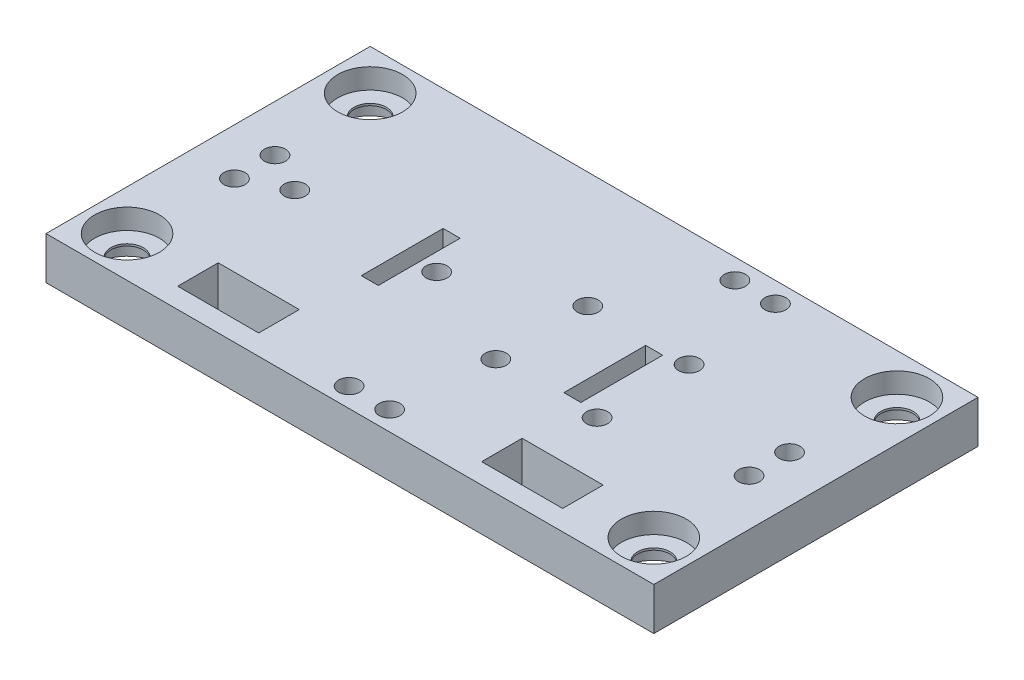
SolidWorks part; units mm, degrees
ref_plane "Front Plane" through (0, 0, 0) normal (0, 0, 1) x (1, 0, 0)
ref_plane "Top Plane" through (0, 0, 0) normal (0, 1, 0) x (1, 0, 0)
ref_plane "Right Plane" through (0, 0, 0) normal (1, 0, 0) x (0, 0, -1)
sketch "Sketch1" plane through (0, 0, 0) normal (0, 1, 0) x (1, 0, 0)
  line L1 (0, 0) -> (150, 0)
  line L2 (0, 0) -> (0, 80)
  line L3 (0, 80) -> (150, 80)
  line L4 (150, 0) -> (150, 80)
  dimension "D1" = 80
  dimension "D2" = 150
extrude "Boss-Extrude1" add sketch "Sketch1" along normal blind 10.5
sketch "Sketch10" plane through (0, 10.5, 0) normal (0, 1, 0) x (1, 0, 0)
  line L0 (75, 80) -> (75, 0) construction
  line L1 (0, 40) -> (150, 40) construction
  line L4 (0, 80) -> (0, 0)
  line L5 (0, 80) -> (0, 0) construction
  line L6 (0, 0) -> (150, 0)
  line L7 (0, 0) -> (150, 0) construction
  line L8 (150, 0) -> (150, 80)
  line L9 (150, 0) -> (150, 80) construction
  line L10 (150, 80) -> (0, 80)
  line L11 (150, 80) -> (0, 80) construction
  circle A0 centre (10, 10) radius 8
  circle A1 centre (140, 10) radius 8
  circle A3 centre (10, 70) radius 8
  circle A4 centre (140, 70) radius 8
  circle A5 centre (10, 10) radius 9
  circle A6 centre (10, 70) radius 9
  circle A7 centre (140, 70) radius 9
  circle A8 centre (140, 10) radius 9
  dimension "D4" = 16
  dimension "D2" = 10
  dimension "D3" = 10
  dimension "D1" = 0
  dimension "D5" = 1
extrude "Cut-Extrude8" cut sketch "Sketch10" against normal blind 5 contours A0 | A3 | A4 | A1 region at (10, 10.5, -10) region at (140, 10.5, -10) region at (10, 10.5, -70) region at (140, 10.5, -70)
ref_plane "MirrorPlane1" through (0, 5.25, 0) normal (0, 1, 0) x (1, 0, 0)
ref_plane "MirrorPlane2" through (0, 0, -40) normal (0, 0, 1) x (1, 0, 0)
ref_plane "MirrorPlane3" through (75, 0, 0) normal (-1, 0, 0) x (0, 0, 1)
mirror "Mirror1" about plane through (0, 5.25, 0) normal (0, 1, 0) of "Cut-Extrude8"
sketch "Sketch3" plane through (0, 10.5, 0) normal (0, 1, 0) x (1, 0, 0)
  line L0 (75, 80) -> (75, 0) construction
  line L5 (150, 80) -> (0, 80) construction
  line L6 (75, 5.775) -> (75, -5.775) construction
  line L7 (0, 0) -> (150, 0) construction
  line L8 (27.5, 15) -> (47.5, 15)
  line L9 (27.5, 15) -> (27.5, 5)
  line L10 (27.5, 5) -> (47.5, 5)
  line L11 (47.5, 15) -> (47.5, 5)
  line L12 (27.5, 15) -> (47.5, 5) construction
  line L13 (27.5, 5) -> (47.5, 15) construction
  line L15 (75, 80) -> (0, 0) construction
  line L16 (122.5, 5) -> (102.5, 5)
  line L17 (102.5, 15) -> (102.5, 5)
  line L18 (122.5, 15) -> (102.5, 15)
  line L19 (122.5, 15) -> (122.5, 5)
  point P0 (37.5, 10)
  point P16 (37.5, 40)
  dimension "D1" = 10
  dimension "D2" = 10
  dimension "D3" = 20
extrude "WireHoles" cut sketch "Sketch3" against normal up to next
sketch "Sketch6" plane through (0, 10.5, 0) normal (0, 1, 0) x (1, 0, 0)
  line L0 (75, 80) -> (75, 0) construction
  line L1 (150, 80) -> (0, 80) construction
  line L2 (0, 0) -> (150, 0) construction
  line L3 (38.9, 40) -> (21.4, 40) construction
  line L4 (73, 28.4) -> (4.8, 28.4) construction
  line L5 (73, 28.4) -> (73, 51.6) construction
  line L6 (73, 51.6) -> (4.8, 51.6) construction
  line L7 (4.8, 28.4) -> (4.8, 51.6) construction
  line L8 (73, 28.4) -> (4.8, 51.6) construction
  line L9 (73, 51.6) -> (4.8, 28.4) construction
  line L10 (38.9, 51.6) -> (38.9, 28.4) construction
  circle A0 centre (21.4, 40) radius 2.6
  circle A1 centre (56.4, 40) radius 2.6
  point P8 (38.9, 40)
  point P18 (75, 40)
  dimension "D5" = 5.2
  dimension "D1" = 68.2
  dimension "D2" = 23.2
  dimension "D3" = 2
  dimension "D4" = 17.5
extrude "4AACut" cut sketch "Sketch6" against normal blind 5.2
sketch "Sketch7" plane through (0, 10.5, 0) normal (0, 1, 0) x (1, 0, 0)
  line L0 (94.85, 51.35) -> (82.35, 51.35) construction
  line L1 (77, 42) -> (112.7, 42) construction
  line L2 (77, 42) -> (77, 60.7) construction
  line L3 (77, 60.7) -> (112.7, 60.7) construction
  line L4 (112.7, 42) -> (112.7, 60.7) construction
  line L5 (77, 42) -> (112.7, 60.7) construction
  line L6 (77, 60.7) -> (112.7, 42) construction
  line L7 (94.85, 60.7) -> (94.85, 42) construction
  line L8 (75, 80) -> (75, 0) construction
  line L9 (150, 80) -> (0, 80) construction
  line L10 (0, 0) -> (150, 0) construction
  line L11 (0, 40) -> (150, 40) construction
  line L12 (0, 80) -> (0, 0) construction
  line L13 (150, 0) -> (150, 80) construction
  circle A0 centre (82.35, 51.35) radius 2.6
  circle A1 centre (56.4, 40) radius 2.6 construction
  circle A2 centre (107.35, 51.35) radius 2.6
  circle A3 centre (82.35, 28.65) radius 2.6
  circle A4 centre (107.35, 28.65) radius 2.6
  point P0 (94.85, 51.35)
  dimension "D1" = 35.7
  dimension "D2" = 18.7
  dimension "D3" = 2
  dimension "D4" = 2
  dimension "D5" = 12.5
extrude "2AACut" cut sketch "Sketch7" against normal blind 5.2
sketch "Sketch5" plane through (0, 10.5, 0) normal (0, 1, 0) x (1, 0, 0)
  line L0 (75, 80) -> (75, 0) construction
  line L5 (150, 80) -> (0, 80) construction
  line L6 (0, 0) -> (150, 0) construction
  line L7 (50, 40) -> (75, 40) construction
  line L12 (47.9, 29.9) -> (52.1, 29.9)
  line L13 (47.9, 29.9) -> (47.9, 50.1)
  line L14 (47.9, 50.1) -> (52.1, 50.1)
  line L15 (52.1, 29.9) -> (52.1, 50.1)
  line L16 (47.9, 29.9) -> (52.1, 50.1) construction
  line L17 (47.9, 50.1) -> (52.1, 29.9) construction
  line L18 (102.1, 50.1) -> (97.9, 50.1)
  line L19 (97.9, 29.9) -> (97.9, 50.1)
  line L20 (102.1, 29.9) -> (97.9, 29.9)
  line L21 (102.1, 29.9) -> (102.1, 50.1)
  point P0 (50, 40)
  dimension "D1" = 25
  dimension "D2" = 4.2
  dimension "D3" = 20.2
extrude "ArduinoMegaCut" cut sketch "Sketch5" against normal blind 5.2
sketch "Sketch8" plane through (0, 10.5, 0) normal (0, 1, 0) x (1, 0, 0)
  line L0 (150, 80) -> (0, 80) construction
  line L5 (62.4, -2.5) -> (87.6, -2.5) construction
  line L6 (62.4, -2.5) -> (62.4, 12.1) construction
  line L7 (62.4, 12.1) -> (87.6, 12.1) construction
  line L8 (87.6, -2.5) -> (87.6, 12.1) construction
  line L9 (75, 80) -> (75, 0) construction
  line L10 (0, 0) -> (150, 0) construction
  line L11 (87.6, 4.8) -> (62.4, 4.8) construction
  circle A1 centre (70, 4.8) radius 2.6
  circle A2 centre (56.4, 40) radius 2.6 construction
  circle A3 centre (80, 4.8) radius 2.6
  point P10 (75, 12.1)
  dimension "D1" = 14.6
  dimension "D2" = 25.2
  dimension "D3" = 2.5
  dimension "D4" = 5
extrude "MPUCut" cut sketch "Sketch8" against normal blind 5.2
sketch "Sketch9" plane through (0, 10.5, 0) normal (0, 1, 0) x (1, 0, 0)
  line L0 (150, 0) -> (150, 80) construction
  line L1 (127, 51.225) -> (150, 51.225)
  line L2 (127, 51.225) -> (127, 28.775)
  line L3 (127, 28.775) -> (150, 28.775)
  line L4 (150, 51.225) -> (150, 28.775)
  line L5 (127, 51.225) -> (150, 28.775) construction
  line L6 (127, 28.775) -> (150, 51.225) construction
  line L9 (0, 40) -> (150, 40) construction
  line L10 (0, 80) -> (0, 0) construction
  line L11 (75, 80) -> (75, 0) construction
  line L12 (150, 80) -> (0, 80) construction
  line L13 (0, 0) -> (150, 0) construction
  circle A0 centre (138.5, 45) radius 2.6
  circle A1 centre (107.35, 51.35) radius 2.6 construction
  circle A2 centre (138.5, 35) radius 2.6
  circle A3 centre (11.5, 35) radius 2.6
  circle A4 centre (11.5, 45) radius 2.6
  point P0 (138.5, 40)
  dimension "D1" = 22.45
  dimension "D2" = 23
  dimension "D3" = 5
extrude "Cut-Extrude7" cut sketch "Sketch9" against normal up to next contours A0 | A2 | A4 | A3 region at (138.5, 10.5, -45) region at (138.5, 10.5, -35) region at (11.5, 10.5, -45)
sketch "Sketch11" plane through (0, 5.5, 0) normal (0, 1, 0) x (1, 0, 0)
  line L0 (0, 40) -> (150, 40) construction
  line L1 (0, 80) -> (0, 0) construction
  line L2 (150, 0) -> (150, 80) construction
  line L3 (75, 80) -> (75, 0) construction
  line L4 (150, 80) -> (0, 80) construction
  line L5 (0, 0) -> (150, 0) construction
  circle A0 centre (10, 10) radius 4
  circle A1 centre (10, 70) radius 4
  circle A2 centre (140, 70) radius 4
  circle A3 centre (140, 10) radius 4
  dimension "D1" = 8
extrude "Cut-Extrude9" cut sketch "Sketch11" against normal up to surface (0.5 mm away) up to face at (10, 5, -62)
sketch "Sketch12" plane through (0, 10.5, 0) normal (0, 1, 0) x (1, 0, 0)
  line L0 (100, 80) -> (100, 0) construction
  line L1 (150, 80) -> (0, 80) construction
  line L2 (0, 0) -> (150, 0) construction
  line L3 (150, 0) -> (150, 80) construction
  circle A0 centre (95, 75) radius 2.6
  circle A1 centre (82.35, 51.35) radius 2.6 construction
  circle A4 centre (105, 75) radius 2.6
  dimension "D1" = 50
  dimension "D2" = 10
  dimension "D3" = 5
extrude "Cut-Extrude10" cut sketch "Sketch12" against normal blind 5
equation "\"Depth\"= 5.20"
